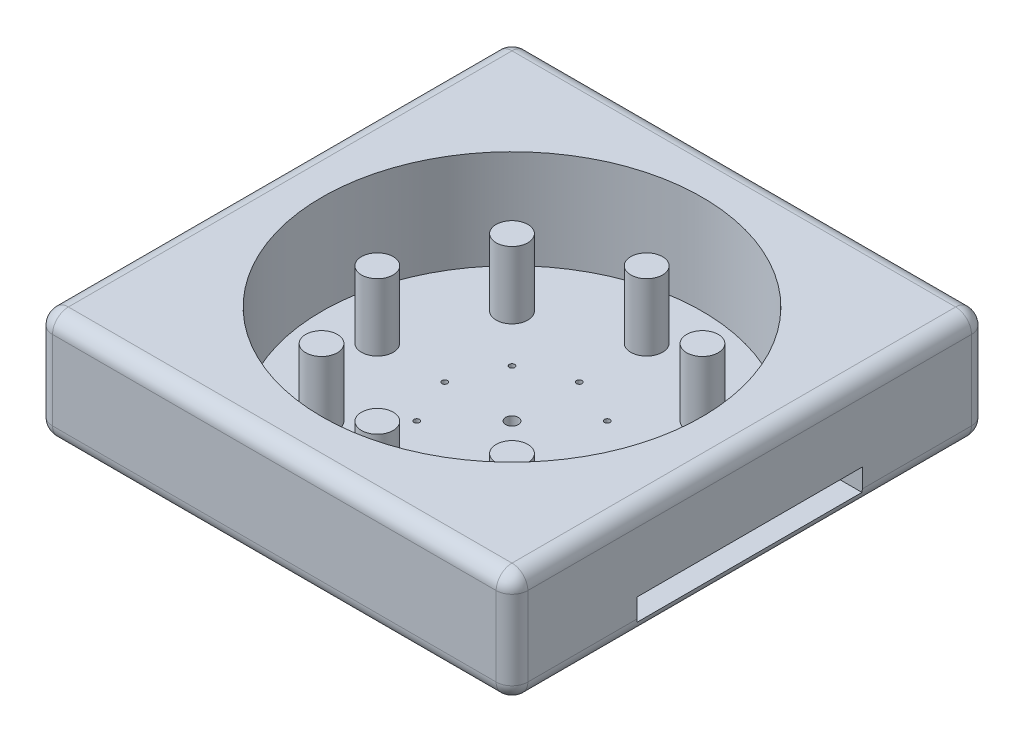
SolidWorks part; units mm, degrees
ref_plane "前视基准面" through (0, 0, 0) normal (0, 0, 1) x (1, 0, 0)
ref_plane "上视基准面" through (0, 0, 0) normal (0, 1, 0) x (1, 0, 0)
ref_plane "右视基准面" through (0, 0, 0) normal (1, 0, 0) x (0, 0, -1)
other "Configuration Table"
sketch "草图1" plane through (0, 0, 0) normal (0, 1, 0) x (1, 0, 0)
  line L1 (-150, 150) -> (150, 150)
  line L2 (-150, 150) -> (-150, -150)
  line L3 (-150, -150) -> (150, -150)
  line L4 (150, 150) -> (150, -150)
  line L5 (-150, 150) -> (150, -150) construction
  line L6 (-150, -150) -> (150, 150) construction
  point P0 (0, 0)
  dimension "D1" = 300
  dimension "D2" = 300
extrude "凸台-拉伸1" add sketch "草图1" along normal blind 150
sketch "草图2" plane through (0, 150, 0) normal (0, 1, 0) x (1, 0, 0)
  circle A0 centre (0, 0) radius 120
extrude "切除-拉伸1" cut sketch "草图2" against normal blind 62.3
sketch "草图3" plane through (0, 87.7, 0) normal (0, 1, 0) x (1, 0, 0)
  circle A1 centre (42.5, 0) radius 1.75
  circle A2 centre (30.052, -30.052) radius 1.75
  circle A3 centre (0, -42.5) radius 1.75
  circle A4 centre (-30.052, -30.052) radius 1.75
  circle A5 centre (-42.5, 0) radius 1.75
  circle A6 centre (-30.052, 30.052) radius 1.75
  circle A7 centre (0, 42.5) radius 1.75
  circle A8 centre (30.052, 30.052) radius 1.75
  circle A9 centre (0, 0) radius 4
  point P21 (0, 0)
  dimension "D1" = 3.5
  dimension "D2" = 8
extrude "切除-拉伸2" cut sketch "草图3" against normal blind 10
sketch "草图6" plane through (150, 0, 0) normal (1, 0, 0) x (0, 0, -1)
  line L0 (0, 150) -> (0, 95) construction
  line L1 (-150, 150) -> (150, 150) construction
  line L7 (-71.0782, 102) -> (71.0782, 102)
  line L8 (-71.0782, 102) -> (-71.0782, 88)
  line L9 (-71.0782, 88) -> (71.0782, 88)
  line L10 (71.0782, 102) -> (71.0782, 88)
  line L11 (-71.0782, 102) -> (71.0782, 88) construction
  line L12 (-71.0782, 88) -> (71.0782, 102) construction
  dimension "D1" = 14
extrude "切除-拉伸4" cut sketch "草图6" against normal blind 75
sketch "草图11" plane through (0, 87.7, 0) normal (0, 1, 0) x (1, 0, 0)
  circle A1 centre (-85, 0) radius 10
  circle A2 centre (-60.1041, 60.1041) radius 10
  circle A3 centre (0, 85) radius 10
  circle A4 centre (60.1041, 60.1041) radius 10
  circle A5 centre (85, 0) radius 10 [skipped]
  circle A6 centre (60.1041, -60.1041) radius 10
  circle A7 centre (0, -85) radius 10
  circle A8 centre (-60.1041, -60.1041) radius 10
  point P22 (0, 0)
  dimension "D2" = 8
extrude "凸台-拉伸4" add sketch "草图11" along normal blind 42.3
fillet "圆角1" radius 10 12 edges at (-150, 0, 0) (0, 0, -150) (-150, 75, -150) (0, 150, -150) (150, 75, -150) (0, 0, 150) (150, 75, 150) (150, 0, 0) (150, 150, 0) (-150, 75, 150) (0, 150, 150) (-150, 150, 0)
sketch "草图12" plane through (0, 0, 0) normal (0, -1, 0) x (1, 0, 0)
  line L0 (0, 140) -> (0, -140) construction
  line L1 (140, 140) -> (-140, 140) construction
  line L2 (-140, -140) -> (140, -140) construction
  line L3 (-140, 0) -> (140, 0) construction
  line L4 (-140, 140) -> (-140, -140) construction
  line L5 (140, -140) -> (140, 140) construction
sketch "草图13" plane through (0, 0, 0) normal (0, -1, 0) x (1, 0, 0)
  line L0 (0, 140) -> (0, -140) construction
  line L1 (-150, 150) -> (150, 150)
  line L2 (-150, 150) -> (-150, -150)
  line L3 (-150, -150) -> (150, -150)
  line L4 (150, 150) -> (150, -150)
  line L5 (-150, 150) -> (150, -150) construction
  line L6 (-150, -150) -> (150, 150) construction
  point P0 (0, 0)
extrude "切除-拉伸5" cut sketch "草图13" against normal blind 80
sketch "草图14" plane through (0, 80, 0) normal (0, -1, 0) x (1, 0, 0)
  line L0 (0, 140) -> (0, -140) construction
  line L1 (0, 104.5637) -> (0, -150) construction
  line L2 (-140, -150) -> (140, -150) construction
  circle A0 centre (0, 104.5637) radius 25
  circle A1 centre (-112.8152, -110.2451) radius 25
  circle A2 centre (112.8152, -110.2451) radius 25
extrude "凸台-拉伸5" add sketch "草图14" along normal blind 5
fillet "圆角2" radius 10 8 edges at (147.0711, 80, 147.0711) (147.0711, 80, -147.0711) (-147.0711, 80, -147.0711) (-147.0711, 80, 147.0711) (-150, 80, 0) (0, 80, -150) (150, 80, 0) (0, 80, 150)
